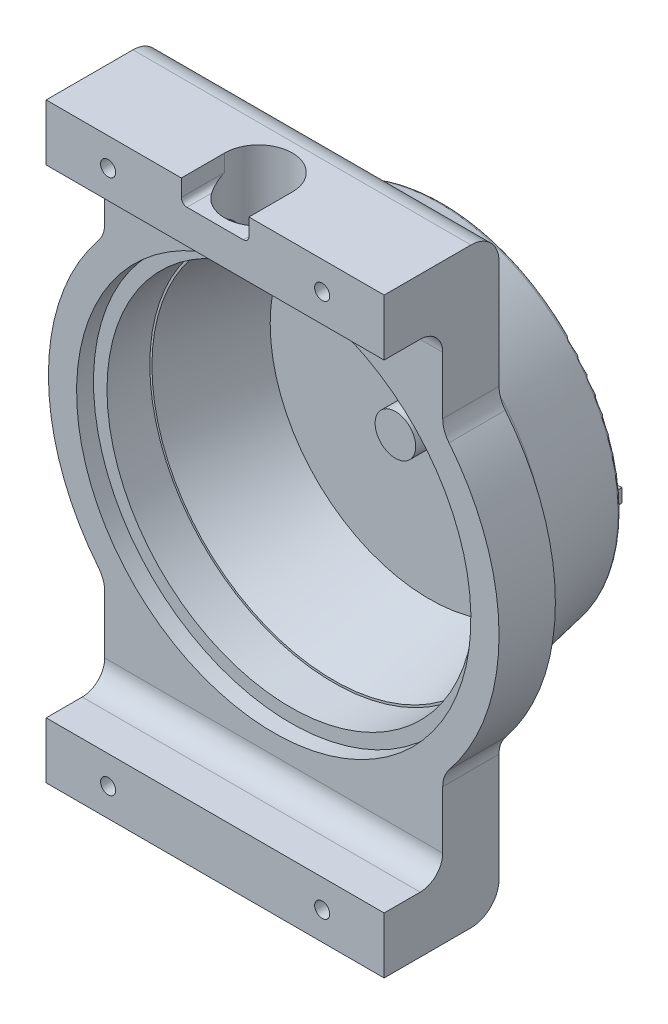
SolidWorks part; units mm, degrees
ref_plane "Front Plane" through (0, 0, 0) normal (0, 0, 1) x (1, 0, 0)
ref_plane "Top Plane" through (0, 0, 0) normal (0, 1, 0) x (1, 0, 0)
ref_plane "Right Plane" through (0, 0, 0) normal (1, 0, 0) x (0, 0, -1)
ref_plane "Plane1" through (0, 0, 1247.394) normal (0, 0, 1) x (1, 0, 0)
sketch "Sketch1" plane through (0, 0, 1247.394) normal (0, 0, 1) x (1, 0, 0)
  line L0 (632.6886, 939.981) -> (632.6886, 906.907)
  line L1 (632.6886, 906.907) -> (708.8886, 906.907)
  line L2 (708.8886, 906.907) -> (708.8886, 939.981)
  line L3 (708.8886, 1007.183) -> (708.8886, 1040.257)
  line L4 (708.8886, 1040.257) -> (632.6886, 1040.257)
  line L5 (632.6886, 1040.257) -> (632.6886, 1007.183)
  arc A0 (708.8886, 939.981) -> (708.8886, 1007.183) centre (670.7886, 973.582) ccw
  arc A1 (632.6886, 1007.183) -> (632.6886, 939.981) centre (670.7886, 973.582) ccw
extrude "Boss-Extrude1" add sketch "Sketch1" against normal blind 12.7
sketch "Sketch2" plane through (0, 0, 1247.394) normal (0, 0, 1) x (1, 0, 0)
  line L0 (708.8886, 1027.557) -> (632.6886, 1027.557)
  line L1 (632.6886, 1027.557) -> (632.6886, 1040.257)
  line L2 (632.6886, 1040.257) -> (708.8886, 1040.257)
  line L3 (708.8886, 1040.257) -> (708.8886, 1027.557)
extrude "Boss-Extrude2" add sketch "Sketch2" along normal blind 13.208
sketch "Sketch3" plane through (0, 0, 1247.394) normal (0, 0, 1) x (1, 0, 0)
  line L0 (708.8886, 906.907) -> (632.6886, 906.907)
  line L1 (632.6886, 906.907) -> (632.6886, 919.607)
  line L2 (632.6886, 919.607) -> (708.8886, 919.607)
  line L3 (708.8886, 919.607) -> (708.8886, 906.907)
extrude "Boss-Extrude3" add sketch "Sketch3" along normal blind 13.208
sketch "Sketch4" plane through (0, 0, 1234.694) normal (0, 0, -1) x (-1, 0, 0)
  circle A0 centre (-670.7886, 973.582) radius 45.212
extrude "Boss-Extrude4" add sketch "Sketch4" along normal blind 25.4 draft 11.231
sketch "Sketch5" plane through (0, 0, 1209.294) normal (0, 0, -1) x (-1, 0, 0)
  line L0 (-708.1266, 972.058) -> (-708.1266, 975.106)
  line L1 (-708.1266, 975.106) -> (-702.2477, 975.106)
  line L2 (-702.2477, 972.058) -> (-708.1266, 972.058)
  arc A0 (-702.2477, 975.106) -> (-702.2477, 972.058) centre (-670.7886, 973.582) cw
extrude "Boss-Extrude5" add sketch "Sketch5" along normal blind 3.048
sketch "Sketch6" plane through (0, 0, 1247.394) normal (0, 0, 1) x (1, 0, 0)
  circle A0 centre (670.7886, 973.582) radius 44.45
extrude "Cut-Extrude1" cut sketch "Sketch6" against normal blind 3.81
sketch "Sketch7" plane through (0, 0, 1243.584) normal (0, 0, 1) x (1, 0, 0)
  circle A0 centre (670.7886, 973.582) radius 41.402
extrude "Cut-Extrude2" cut sketch "Sketch7" against normal blind 9.652
sketch "Sketch8" plane through (0, 0, 1233.932) normal (0, 0, 1) x (1, 0, 0)
  circle A0 centre (670.7886, 973.582) radius 40.9244
extrude "Cut-Extrude3" cut sketch "Sketch8" against normal blind 21.59 draft 13.225
ref_plane "Plane2" through (0, 973.582, 0) normal (0, -1, 0) x (1, 0, 0)
sketch "Sketch9" plane through (0, 973.582, 0) normal (0, -1, 0) x (1, 0, 0)
  line L0 (675.3606, 1219.962) -> (670.7886, 1219.962)
  line L1 (670.7886, 1219.962) -> (670.7886, 1212.342)
  line L2 (670.7886, 1212.342) -> (675.3606, 1212.342)
  line L3 (675.3606, 1212.342) -> (675.3606, 1219.962)
  line L4 (670.7886, 1219.962) -> (670.7886, 1212.342) construction
revolve "Revolve1" add sketch "Sketch9" angle 360 about L4 reverse direction yes
hole_wizard "CBORE for M3 Hex Head Machine Screw1" positions "Sketch13" profile "Sketch12" counterbore size "M3" standard "ANSI Metric"
sketch "Sketch13" plane through (0, 0, 1234.694) normal (0, 0, -1) x (-1, 0, 0)
  point P0 (-694.9186, 1033.907)
  point P1 (-646.6586, 1033.907)
  point P2 (-694.9186, 913.257)
  point P3 (-646.6586, 913.257)
sketch "Sketch12" plane through (694.9186, 1033.907, 1234.694) normal (1, 0, 0) x (0, 1, 0)
  line L0 (0, 0) -> (0, 25.908)
  line L1 (0, 25.908) -> (1.7018, 25.908)
  line L3 (1.7018, 25.908) -> (1.7018, 4.064)
  line L4 (1.7018, 4.064) -> (3.175, 4.064)
  line L5 (3.175, 4.064) -> (3.175, 0)
  line L7 (3.175, 0) -> (0, 0)
  line L11 (0, -6.35) -> (0, 107.95) construction
  dimension "Thru Hole Dia." = 3.4036
  dimension "Thru Hole Depth" = 25.908
  dimension "C'Bore Dia." = 6.35
  dimension "C'Bore Depth" = 4.064
hole_wizard "CBORE for M3.5 Hex Head Machine Screw1" positions "Sketch15" profile "Sketch14" counterbore size "M3.5" standard "ANSI Metric"
sketch "Sketch15" plane through (0, 0, 1206.246) normal (0, 0, -1) x (-1, 0, 0)
  point P0 (-670.7886, 973.582)
sketch "Sketch14" plane through (670.7886, 973.582, 1206.246) normal (1, 0, 0) x (0, 1, 0)
  line L0 (0, 0) -> (0, 6.7564)
  line L1 (0, 6.7564) -> (2.1971, 6.7564)
  line L2 (2.1971, 6.7564) -> (2.1971, 3.048)
  line L3 (2.1971, 3.048) -> (27.94, 3.048)
  line L4 (27.94, 3.048) -> (27.94, 0)
  line L5 (27.94, 0) -> (0, 0)
  line L10 (0, 6.7564) -> (-2.1971, 6.7564) construction
  line L11 (0, -6.35) -> (0, 107.95) construction
  dimension "Hole Dia." = 4.3942
  dimension "Hole Depth" = 6.7564
  dimension "C'Bore Dia." = 55.88
  dimension "C'Bore Depth" = 3.048
  dimension "Drill Angle" = 180
hole_wizard "Hole2" positions "Sketch17" profile "Sketch16" legacy
sketch "Sketch17" plane through (0, 0, 1209.294) normal (0, 0, -1) x (-1, 0, 0)
  point P0 (-670.7886, 995.172)
sketch "Sketch16" plane through (670.7886, 995.172, 1209.294) normal (1, 0, 0) x (0, 1, 0)
  line L0 (0, 0) -> (0, 51.308)
  line L1 (0, 51.308) -> (6.096, 51.308)
  line L2 (6.096, 51.308) -> (6.096, 0)
  line L3 (6.096, 0) -> (0, 0)
  line L4 (0, 110) -> (0, -10) construction
  dimension "Diameter" = 12.192
  dimension "Depth" = 51.308
fillet "Fillet1" radius 1.016 1 edges at (630.6202, 973.582, 1209.294) tangent propagation no
fillet "Fillet2" radius 5.08 2 edges at (670.7886, 1027.557, 1247.394) (670.7886, 919.607, 1247.394) tangent propagation no
fillet "Fillet3" radius 6.35 7 edges at (708.8886, 939.981, 1241.044) (632.6886, 939.981, 1241.044) (625.5766, 973.582, 1234.694) (632.6886, 1007.183, 1241.044) (670.7886, 906.907, 1234.694) (670.7886, 1040.257, 1234.694) (708.8886, 1007.183, 1241.044) tangent propagation no
sketch "Sketch18" plane through (0, 1040.257, 0) normal (0, 1, 0) x (1, 0, 0)
  line L4 (670.7886, -1260.602) -> (670.7886, -1241.044) construction
  line L5 (708.8886, -1260.602) -> (632.6886, -1260.602) construction
  line L6 (708.8886, -1241.044) -> (632.6886, -1241.044) construction
  line L7 (663.1686, -1250.823) -> (663.1686, -1260.602)
  line L8 (663.1686, -1260.602) -> (678.4086, -1260.602)
  line L9 (678.4086, -1260.602) -> (678.4086, -1250.823)
  arc A2 (678.4086, -1250.823) -> (663.1686, -1250.823) centre (670.7886, -1250.823) ccw
  dimension "D1" = 7.62
extrude "Cut-Extrude4" cut sketch "Sketch18" against normal blind 5.08
sketch "Sketch20" plane through (0, 1035.177, 0) normal (0, 1, 0) x (1, 0, 0)
  circle A0 centre (670.7886, -1250.823) radius 7.62
extrude "Cut-Extrude5" cut sketch "Sketch20" against normal up to surface (20.193 mm away) up to face at (629.3866, 973.582, 1233.932)
fillet "Fillet4" radius 1.27 2 edges at (678.4086, 1035.177, 1255.7125) (663.1686, 1035.177, 1255.7125)
